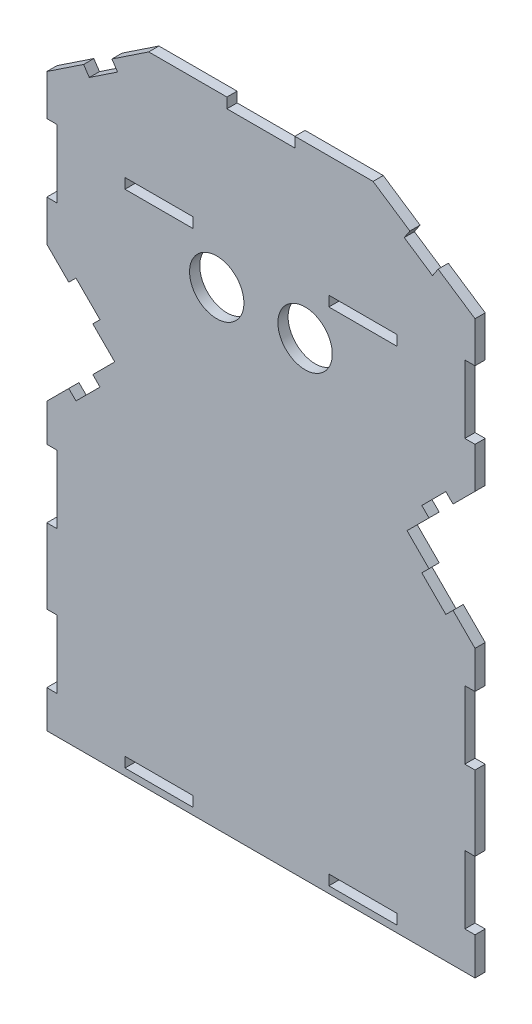
SolidWorks part; units mm, degrees
ref_plane "Front Plane" through (0, 0, 0) normal (0, 0, 1) x (1, 0, 0)
ref_plane "Top Plane" through (0, 0, 0) normal (0, 1, 0) x (1, 0, 0)
ref_plane "Right Plane" through (0, 0, 0) normal (1, 0, 0) x (0, 0, -1)
sketch "Sketch1" plane through (0, 0, 0) normal (0, 0, 1) x (1, 0, 0)
  line L0 (62.2747, 0) -> (62.2747, -11)
  line L1 (-33.7253, 104) -> (-10.7253, 104)
  line L2 (-63.7253, 84) -> (-63.7253, 72)
  line L3 (-63.7253, -84) -> (62.2747, -84)
  line L4 (62.2747, 84) -> (62.2747, 72)
  line L5 (-0.7253, -84) -> (-0.7253, -49.3815) construction
  line L6 (-63.7253, -84) -> (-63.7253, -80.5) construction
  line L7 (-63.7253, -80.5) -> (-60.7253, -80.5) construction
  line L8 (-63.7253, 84) -> (-52.8856, 91.2265)
  line L10 (-63.7253, 84) -> (-63.7253, 72) construction
  line L11 (-60.7253, -80.5) -> (-60.7253, -84) construction
  line L12 (-63.7253, 0) -> (-57.2608, 6.4645)
  line L13 (-43.7253, 20) -> (-50.1898, 26.4645)
  line L14 (62.2747, 0) -> (55.8102, 6.4645)
  line L15 (42.2747, 20) -> (48.7392, 26.4645)
  line L16 (-63.7253, 0) -> (-63.7253, -11)
  line L17 (62.2747, -80.5) -> (59.2747, -80.5) construction
  line L18 (-60.7253, -80.5) -> (59.2747, -80.5) construction
  line L19 (-0.7253, -80.5) -> (-60.7253, -80.5) construction
  line L20 (19.2747, -82) -> (19.2747, -79)
  line L21 (-40.7253, -82) -> (-20.7253, -82)
  line L22 (-40.7253, -82) -> (-40.7253, -79)
  line L23 (-40.7253, -79) -> (-20.7253, -79)
  line L24 (-20.7253, -82) -> (-20.7253, -79)
  line L25 (-40.7253, -82) -> (-20.7253, -79) construction
  line L26 (-40.7253, -79) -> (-20.7253, -82) construction
  line L27 (39.2747, -82) -> (19.2747, -82)
  line L28 (39.2747, -82) -> (39.2747, -79)
  line L29 (39.2747, -79) -> (19.2747, -79)
  line L30 (-63.7253, -84) -> (-62.221, -84) construction
  line L31 (-63.7253, -42) -> (-62.2253, -42) construction
  line L32 (-62.2253, -42) -> (-62.2253, 0) construction
  line L33 (-62.2253, 0) -> (-63.7253, 0) construction
  line L34 (-63.7253, -31) -> (-60.7253, -31)
  line L36 (-63.7253, -11) -> (-60.7253, -11)
  line L37 (-60.7253, -31) -> (-60.7253, -11)
  line L38 (-63.7253, -31) -> (-60.7253, -11) construction
  line L39 (-63.7253, -11) -> (-60.7253, -31) construction
  line L40 (-63.7253, -53) -> (-60.7253, -53)
  line L41 (-60.7253, -53) -> (-60.7253, -73)
  line L42 (-63.7253, -73) -> (-60.7253, -73)
  line L43 (-62.2253, -84) -> (-63.7253, -84) construction
  line L44 (62.2747, -53) -> (59.2747, -53)
  line L45 (59.2747, -53) -> (59.2747, -73)
  line L46 (62.2747, -73) -> (59.2747, -73)
  line L47 (62.2747, -31) -> (59.2747, -31)
  line L48 (62.2747, -11) -> (59.2747, -11)
  line L49 (59.2747, -31) -> (59.2747, -11)
  line L50 (-63.7253, -73) -> (-63.7253, -84)
  line L51 (62.2747, -73) -> (62.2747, -84)
  line L52 (62.2747, -31) -> (62.2747, -53)
  line L53 (-63.7253, -31) -> (-63.7253, -53)
  line L54 (-63.7253, 40) -> (-62.2253, 40) construction
  line L55 (-62.2253, 40) -> (-62.2253, 84) construction
  line L56 (-62.2253, 84) -> (-63.7253, 84) construction
  line L57 (-63.7253, 52) -> (-63.7253, 40)
  line L58 (-63.7253, 52) -> (-60.7253, 52)
  line L60 (-63.7253, 72) -> (-60.7253, 72)
  line L61 (-60.7253, 52) -> (-60.7253, 72)
  line L62 (-63.7253, 52) -> (-60.7253, 72) construction
  line L63 (-63.7253, 72) -> (-60.7253, 52) construction
  line L64 (-63.7253, 52) -> (-63.7253, 40) construction
  line L65 (62.2747, 52) -> (59.2747, 52)
  line L66 (59.2747, 52) -> (59.2747, 72)
  line L67 (62.2747, 72) -> (59.2747, 72)
  line L68 (62.2747, 52) -> (62.2747, 40)
  line L69 (-43.7253, 20) -> (-42.6646, 18.9393) construction
  line L70 (-63.7253, 0) -> (-62.6646, -1.0607) construction
  line L71 (-62.6646, -1.0607) -> (-42.6646, 18.9393) construction
  line L72 (-55.1395, 4.3431) -> (-57.2608, 6.4645)
  line L73 (-55.1395, 4.3431) -> (-48.0685, 11.4142)
  line L75 (-48.0685, 11.4142) -> (-50.1898, 13.5355)
  line L76 (-50.1898, 13.5355) -> (-43.7253, 20)
  line L77 (53.6889, 4.3431) -> (55.8102, 6.4645)
  line L78 (46.6178, 11.4142) -> (48.7392, 13.5355)
  line L79 (53.6889, 4.3431) -> (46.6178, 11.4142)
  line L80 (42.2747, 20) -> (5.8268, 20) construction
  line L81 (-55.1395, 35.6569) -> (-57.2608, 33.5355)
  line L82 (-48.0685, 28.5858) -> (-50.1898, 26.4645)
  line L83 (-55.1395, 35.6569) -> (-48.0685, 28.5858)
  line L84 (-57.2608, 33.5355) -> (-63.7253, 40)
  line L85 (46.6178, 28.5858) -> (48.7392, 26.4645)
  line L86 (53.6889, 35.6569) -> (55.8102, 33.5355)
  line L87 (53.6889, 35.6569) -> (46.6178, 28.5858)
  line L88 (55.8102, 33.5355) -> (62.2747, 40)
  line L89 (48.7392, 13.5355) -> (42.2747, 20)
  line L90 (-63.7253, 84) -> (-52.8856, 91.2265) construction
  line L92 (-52.8856, 91.2265) -> (-51.2215, 88.7303)
  line L93 (-44.5651, 96.7735) -> (-42.901, 94.2774)
  line L94 (-51.2215, 88.7303) -> (-42.901, 94.2774)
  line L95 (-44.5651, 96.7735) -> (-33.7253, 104)
  line L96 (-44.5651, 96.7735) -> (-33.7253, 104) construction
  line L97 (-33.7253, 104) -> (-63.7253, 84) construction
  line L98 (-48.7253, 94) -> (-47.0612, 91.5038) construction
  line L99 (51.4349, 91.2265) -> (49.7708, 88.7303)
  line L100 (49.7708, 88.7303) -> (41.4503, 94.2774)
  line L101 (43.1144, 96.7735) -> (41.4503, 94.2774)
  line L102 (32.2747, 104) -> (43.1144, 96.7735)
  line L103 (62.2747, 84) -> (51.4349, 91.2265)
  line L104 (-33.7253, 104) -> (-33.7253, 102.5) construction
  line L105 (-33.7253, 102.5) -> (32.2747, 102.5) construction
  line L106 (32.2747, 102.5) -> (32.2747, 104) construction
  line L107 (-10.7253, 101) -> (9.2747, 101)
  line L108 (-10.7253, 101) -> (-10.7253, 104)
  line L110 (9.2747, 101) -> (9.2747, 104)
  line L111 (-10.7253, 101) -> (9.2747, 104) construction
  line L112 (-10.7253, 104) -> (9.2747, 101) construction
  line L113 (9.2747, 104) -> (32.2747, 104)
  line L114 (-63.7253, 84) -> (62.2747, 84) construction
  line L115 (-0.7253, 84) -> (-0.7253, 67) construction
  line L116 (-0.7253, 67) -> (-60.7253, 67) construction
  line L117 (39.2747, 65.5) -> (39.2747, 68.5)
  line L118 (-40.7253, 65.5) -> (-20.7253, 65.5)
  line L119 (-40.7253, 65.5) -> (-40.7253, 68.5)
  line L120 (-40.7253, 68.5) -> (-20.7253, 68.5)
  line L121 (-20.7253, 65.5) -> (-20.7253, 68.5)
  line L122 (-40.7253, 65.5) -> (-20.7253, 68.5) construction
  line L123 (-40.7253, 68.5) -> (-20.7253, 65.5) construction
  line L124 (39.2747, 65.5) -> (19.2747, 65.5)
  line L125 (19.2747, 65.5) -> (19.2747, 68.5)
  line L126 (39.2747, 68.5) -> (19.2747, 68.5)
  line L127 (-0.7253, 84) -> (-0.7253, 54) construction
  line L128 (-0.7253, 54) -> (-13.7253, 54) construction
  circle A0 centre (-13.7253, 54) radius 8
  circle A1 centre (12.2747, 54) radius 8
  point P0 (0, 0)
  point P20 (-30.7253, -80.5)
  point P31 (-62.2253, -21)
  point P53 (-62.2253, 62)
  point P67 (-52.6646, 8.9393)
  point P94 (-0.7253, 102.5)
  point P103 (-30.7253, 67)
  dimension "D39" = 16
  dimension "D1" = 84
  dimension "D2" = 126
  dimension "D3" = 20
  dimension "D4" = 30
  dimension "D5" = 20
  dimension "D6" = 20
  dimension "D7" = 44
  dimension "D8" = 20
  dimension "D9" = 30
  dimension "D10" = 20
  dimension "D11" = 20
  dimension "D12" = 84
  dimension "D13" = 44
  dimension "D14" = 20
  dimension "D15" = 3
  dimension "D16" = 3.5
  dimension "D17" = 20
  dimension "D18" = 3
  dimension "D19" = 1.5
  dimension "D20" = 20
  dimension "D21" = 3
  dimension "D22" = 1.5
  dimension "D23" = 1.5
  dimension "D24" = 20
  dimension "D25" = 3
  dimension "D26" = 10
  dimension "D27" = 1.5
  dimension "D28" = 48.0685
  dimension "D29" = 10
  dimension "D30" = 3
  dimension "D31" = 17
  dimension "D32" = 20
  dimension "D33" = 3
  dimension "D34" = 60
  dimension "D35" = 20
  dimension "D36" = 3
  dimension "D37" = 30
  dimension "D38" = 13
extrude "Boss-Extrude1" add sketch "Sketch1" along normal blind 3
